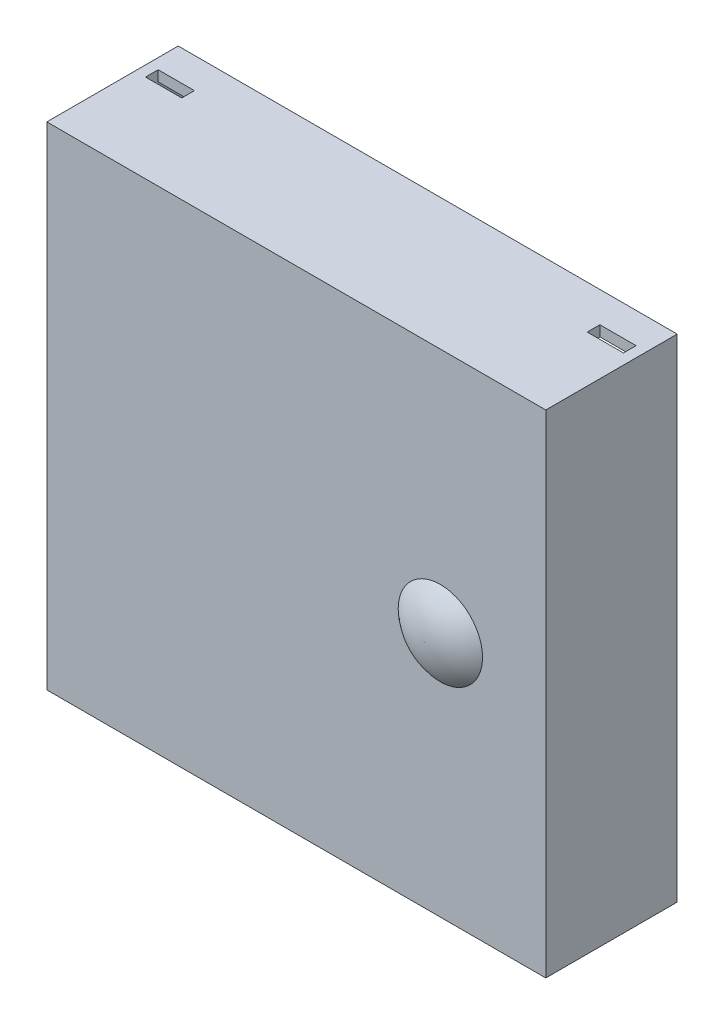
SolidWorks part; units mm, degrees
ref_plane "Front Plane" through (0, 0, 0) normal (0, 0, 1) x (1, 0, 0)
ref_plane "Top Plane" through (0, 0, 0) normal (0, 1, 0) x (1, 0, 0)
ref_plane "Right Plane" through (0, 0, 0) normal (1, 0, 0) x (0, 0, -1)
sketch "Sketch1" plane through (0, 0, 0) normal (0, 0, 1) x (1, 0, 0)
  line L0 (10.75, -9.75) -> (-121.1, -9.75) construction
  line L1 (10.75, 60.25) -> (-60.25, 60.25)
  line L2 (10.75, 60.25) -> (10.75, -9.75)
  line L3 (10.75, -9.75) -> (-60.25, -9.75)
  line L4 (-60.25, 60.25) -> (-60.25, -9.75)
  line L5 (9.25, 58.75) -> (-58.75, 58.75)
  line L6 (-58.75, 58.75) -> (-58.75, -8.25)
  line L7 (9.25, -8.25) -> (-58.75, -8.25)
  line L8 (9.25, 58.75) -> (9.25, -8.25)
  dimension "D1" = 71
  dimension "D2" = 1.5
extrude "Boss-Extrude1" add sketch "Sketch1" along normal blind 17.2
extrude "Boss-Extrude2" add sketch "Sketch1<2>" along normal blind 1.5 from surface contours L4 L3 L2 L1 starting at face at (-24.75, 25.25, 17.2)
sketch "Sketch1<2>" plane through (0, 0, 0) normal (0, 0, 1) x (1, 0, 0) same geometry as "Sketch1"
sketch "Sketch3" plane through (0, 60.25, 0) normal (0, 1, 0) x (1, 0, 0)
  line L0 (-58.75, -3) -> (-60.25, -3) construction
  line L1 (-58.75, -3) -> (-57.25, -3)
  line L2 (-58.75, -3) -> (-58.75, 0)
  line L3 (-58.75, 0) -> (-57.25, 0)
  line L4 (-57.25, -3) -> (-57.25, 0)
  line L5 (-60.25, -18.7) -> (-60.25, 0) construction
  line L6 (10.75, 0) -> (-121.1, 0) construction
  dimension "D1" = 1.5
  dimension "D2" = 3
sketch "Sketch4" plane through (-60.25, 0, 0) normal (-1, 0, 0) x (0, 0, 1)
  line L0 (3, 60.25) -> (0, 60.25) construction
  line L1 (3, 60.25) -> (-4.5, 60.25)
  line L2 (0, -9.75) -> (0, 60.25) construction
  line L3 (1.5, 61.75) -> (-4.5, 61.75)
  line L4 (0, 60.25) -> (-36.6375, 60.25) construction
  line L5 (3, 60.25) -> (0, 60.25) construction
  line L6 (3, 60.25) -> (1.5, 61.75)
  line L7 (1.5, 61.75) -> (1.5, 60.25) construction
  line L8 (-36.6375, 58.75) -> (-33.4875, 58.75) construction
  line L9 (-4.5, 61.75) -> (-6, 61.75)
  line L10 (-4.5, 61.75) -> (-4.5, 58.75)
  line L12 (-6, 61.75) -> (-6, 60.25)
  line L13 (-4.5, 58.75) -> (-6, 60.25)
  dimension "D1" = 1.5
  dimension "D2" = 3
  dimension "D3" = 45
  dimension "D4" = 6
ref_plane "Plane1" through (0, 25.25, 0) normal (0, 1, 0) x (1, 0, 0)
ref_plane "Plane2" through (-24.75, 0, 0) normal (1, 0, 0) x (0, 0, -1)
ref_plane "Plane3" through (0, 0, 20.975) normal (0, 0, 1) x (1, 0, 0)
sketch "Sketch5" plane through (0, 0, 18.7) normal (0, 0, 1) x (1, 0, 0)
  line L0 (10.75, 60.25) -> (10.75, -9.75) construction
  line L1 (1.75, 25.25) -> (10.75, 25.25) construction
  circle A0 centre (-4.25, 25.25) radius 6
  point P4 (10.75, 25.25)
  dimension "D1" = 12
  dimension "D2" = 9
extrude "Boss-Extrude5" add sketch "Sketch5" along normal up to surface (2.275 mm away) up to plane "Plane3"
fillet "Fillet1" radius 9 1 edges at (1.75, 25.25, 20.975)
sketch "Sketch6" plane through (0, 60.25, 0) normal (0, 1, 0) x (1, 0, 0)
  line L4 (9.25, -17.2) -> (9.25, 0) construction
  line L5 (9.25, -17.2) -> (9.25, 0) construction
  line L8 (4.1, -6.15) -> (9.4, -6.15)
  line L9 (9.4, -6.15) -> (9.4, -4.35)
  line L10 (4.1, -4.35) -> (4.1, -6.15)
  line L11 (9.4, -4.35) -> (4.1, -4.35)
  line L12 (4.1, -6.15) -> (9.25, -6.15)
  line L13 (9.25, -6.15) -> (9.25, -4.35)
  line L14 (4.1, -4.35) -> (4.1, -6.15)
  line L15 (9.25, -4.35) -> (4.1, -4.35)
  dimension "D1" = 0.15
extrude "Cut-Extrude1" cut sketch "Sketch6" against normal up to next
mirror "Mirror1" about plane through (-24.75, 0, 0) normal (1, 0, 0) of "Cut-Extrude1"
mirror "Mirror2" about plane through (0, 25.25, 0) normal (0, 1, 0) of "Mirror1", "Cut-Extrude1"
equation "\"D1@Boss-Extrude1\"=14.2+3"
